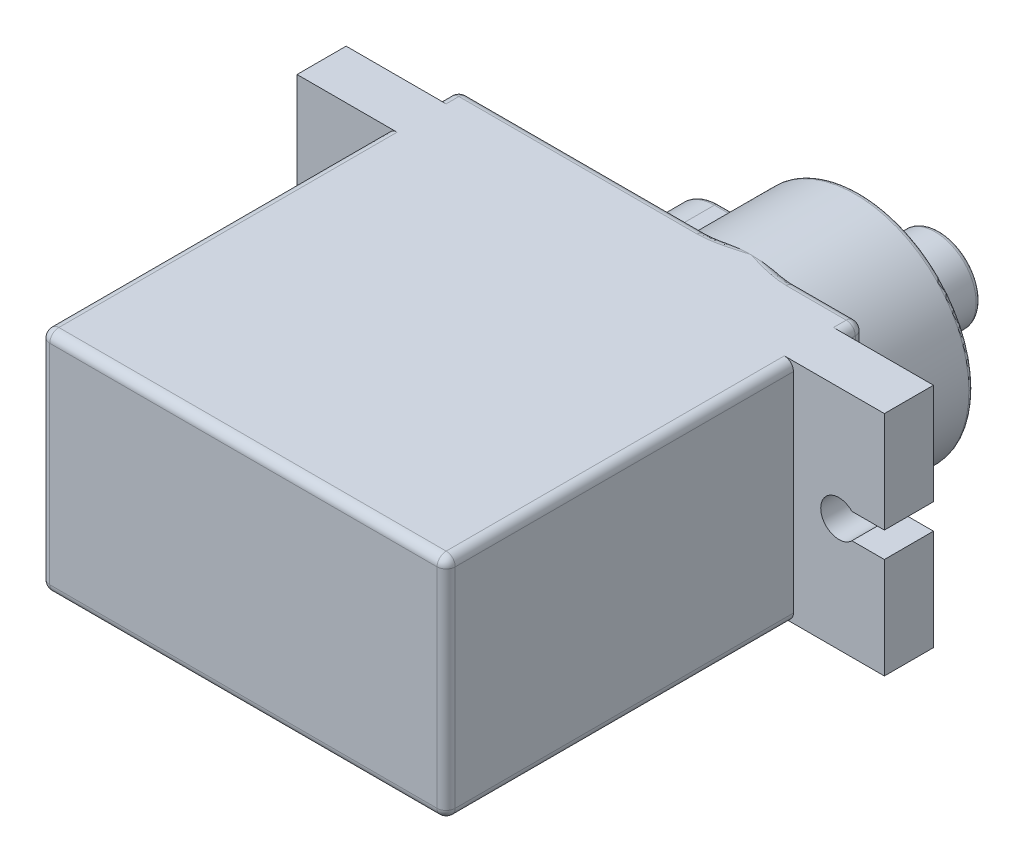
SolidWorks part; units mm, degrees
ref_plane "Přední rovina" through (0, 0, 0) normal (0, 0, 1) x (1, 0, 0)
ref_plane "Horní rovina" through (0, 0, 0) normal (0, 1, 0) x (1, 0, 0)
ref_plane "Pravá rovina" through (0, 0, 0) normal (1, 0, 0) x (0, 0, -1)
sketch "Skica1" plane through (0, 0, 0) normal (0, 0, 1) x (1, 0, 0)
  line L1 (0, 0) -> (22.3, 0)
  line L2 (0, 0) -> (0, -12.5)
  line L3 (0, -12.5) -> (22.3, -12.5)
  line L4 (22.3, 0) -> (22.3, -12.5)
  dimension "D1" = 22.3
  dimension "D2" = 12.5
extrude "Přidat vysunutím1" add sketch "Skica1" along normal blind 23
ref_plane "Rovina1" through (11.15, 0, 0) normal (1, 0, 0) x (0, 0, -1)
sketch "Skica5" plane through (22.3, 0, 0) normal (1, 0, 0) x (0, 0, -1)
  line L0 (-23, 0) -> (0, 0) construction
  line L1 (-3.9, 0) -> (-1.2, 0)
  line L2 (-3.9, 0) -> (-3.9, -12.5)
  line L3 (-3.9, -12.5) -> (-1.2, -12.5)
  line L4 (-1.2, 0) -> (-1.2, -12.5)
  line L5 (-23, -12.5) -> (0, -12.5) construction
  line L6 (-23, -12.5) -> (-23, 0) construction
  dimension "D1" = 2.7
  dimension "D2" = 19.1
extrude "Přidat vysunutím2" add sketch "Skica5" along normal blind 5
sketch "Skica6" plane through (0, 0, 1.2) normal (0, 0, -1) x (-1, 0, 0)
  line L0 (-27.3, -12.5) -> (-27.3, 0) construction
  line L1 (-27.3, -12.5) -> (-22.3, -12.5) construction
  line L2 (-27.3, -5.55) -> (-25.5141, -5.55)
  line L3 (-27.3, -6.95) -> (-25.5141, -6.95)
  line L4 (-27.3, -5.55) -> (-27.3, -6.95) construction
  line L5 (-27.3, -5.55) -> (-27.3, -6.95)
  circle A0 centre (-24.8, -6.25) radius 1
  point P4 (-27.3, -6.25)
  point P7 (-24.8, -12.5)
  point P12 (-27.3, -6.25)
  line M6 (-27.3, 0) -> (-27.3, -12.5)
  dimension "D2" = 2
  dimension "D1" = 1.4
extrude "Odebrat vysunutím2" cut sketch "Skica6" against normal up to surface (2.7 mm away) contours A0 L2 L3 M6 | A0 L5 region at (26.5033, -6.25, 1.2) region at (24.8, -6.25, 1.2) up to face at (24.8, -6.25, 3.9)
sketch "Skica7" plane through (0, 0, 1.2) normal (0, 0, -1) x (-1, 0, 0)
  line L0 (-27.3, 0) -> (-22.3, 0) construction
  line L1 (-27.3, -12.5) -> (-22.3, -12.5) construction
  circle A0 centre (-24.8, -9.75) radius 1
  circle A1 centre (-24.8, -2.75) radius 1
  point P4 (0, 0)
  point P7 (-24.8, 0)
  dimension "D1" = 2
  dimension "D2" = 2.75
  dimension "D3" = 2.75
extrude "Odebrat vysunutím3" cut sketch "Skica7" against normal blind 1
fillet "Zaoblit2" radius 1 2 edges at (24.8, -1.75, 2.2) (24.8, -8.75, 2.2)
mirror "Zrcadlit1" about plane through (11.15, 0, 0) normal (1, 0, 0) of "Zaoblit2", "Odebrat vysunutím3", "Odebrat vysunutím2", "Přidat vysunutím2"
sketch "Skica8" plane through (0, 0, 0) normal (0, 0, -1) x (-1, 0, 0)
  line L2 (-22.3, -12.5) -> (-22.3, 0) construction
  line L4 (0, -12.5) -> (-22.3, -12.5) construction
  line L5 (-22.3, 0) -> (0, 0) construction
  circle A0 centre (-16.05, -6.25) radius 6.25
  point P2 (-15.4472, -6.2691)
extrude "Přidat vysunutím3" add sketch "Skica8" along normal blind 6
sketch "Skica9" plane through (0, 0, 0) normal (0, 0, -1) x (-1, 0, 0)
  line L0 (0, 0) -> (0, -12.5) construction
  circle A0 centre (-8.8, -6.25) radius 2.35
  arc A1 (-16.05, -12.5) -> (-16.05, 0) centre (-16.05, -6.25) ccw construction
  point P5 (0, 0)
  point P6 (-8.8019, -6.4164)
  point P9 (0, -6.25)
  point P10 (0, 0)
  point P11 (0, 0)
  dimension "D1" = 7.25
  dimension "D2" = 4.7
extrude "Přidat vysunutím4" add sketch "Skica9" along normal offset from surface (5.5 mm away) 0.5 up to face at (9.8, -6.25, -6)
ref_plane "Rovina2" through (8.8, 0, 0) normal (-1, 0, 0) x (0, 0, 1)
sketch "Skica10" plane through (8.8, 0, 0) normal (-1, 0, 0) x (0, 0, 1)
  line L5 (-5.5, -3.9) -> (0, -3.9)
  line L6 (-5.5, -3.9) -> (-5.5, -8.6)
  line L7 (-5.5, -8.6) -> (0, -8.6)
  line L8 (0, -3.9) -> (0, -8.6)
extrude "Přidat vysunutím5" add sketch "Skica10" against normal up to surface (1.4586 mm away) up to face at (9.8, -6.25, -6)
sketch "Skica11" plane through (0, 0, -6) normal (0, 0, -1) x (-1, 0, 0)
  circle A0 centre (-16.05, -6.25) radius 2.5
  circle A1 centre (-16.05, -6.25) radius 6.25 construction
  dimension "D1" = 5
extrude "Odebrat vysunutím4" cut sketch "Skica11" against normal blind 2
fillet "Zaoblit3" radius 0.5 19 edges at (22.3, -3.125, 0) (19.175, -12.5, 0) (11.15, 0, 23) (22.3, -6.25, 23) (11.15, -12.5, 23) (0, -6.25, 23) (0, -12.5, 13.45) (22.3, -12.5, 13.45) (22.3, 0, 13.45) (22.3, 0, 0.6) (0, 0, 0.6) (0, 0, 13.45) (22.3, -9.375, 0) (8.025, -12.5, 0) (0, -6.25, 0) (19.175, 0, 0) (8.025, 0, 0) (0, -12.5, 0.6) (22.3, -12.5, 0.6)
sketch "Skica12" plane through (0, 0, -4) normal (0, 0, -1) x (-1, 0, 0)
  circle A0 centre (-16.05, -6.25) radius 2.25
  circle A1 centre (-16.05, -6.25) radius 2.5 construction
  dimension "D1" = 4.5
extrude "Přidat vysunutím6" add sketch "Skica12" along normal blind 6.4
sketch "Skica13" plane through (0, 0, -10.4) normal (0, 0, -1) x (-1, 0, 0)
  circle A0 centre (-16.05, -6.25) radius 1
  circle A1 centre (-16.05, -6.25) radius 2.25 construction
  dimension "D1" = 2
extrude "Odebrat vysunutím5" cut sketch "Skica13" against normal blind 6.4
fillet "Zaoblit4" radius 0.25 2 edges at (13.8, -6.25, -10.4) (15.05, -6.25, -10.4)
fillet "Zaoblit5" radius 0.25 4 edges at (9.5293, -8.6, -5.5) (6.45, -6.25, -5.5) (9.5293, -3.9, -5.5) (9.8, -6.25, -6)
ref_plane "Rovina3" through (0, -6.25, 0) normal (0, 1, 0) x (1, 0, 0)
ref_plane "Rovina4" through (0, 0, 11.5) normal (0, 0, 1) x (1, 0, 0)
